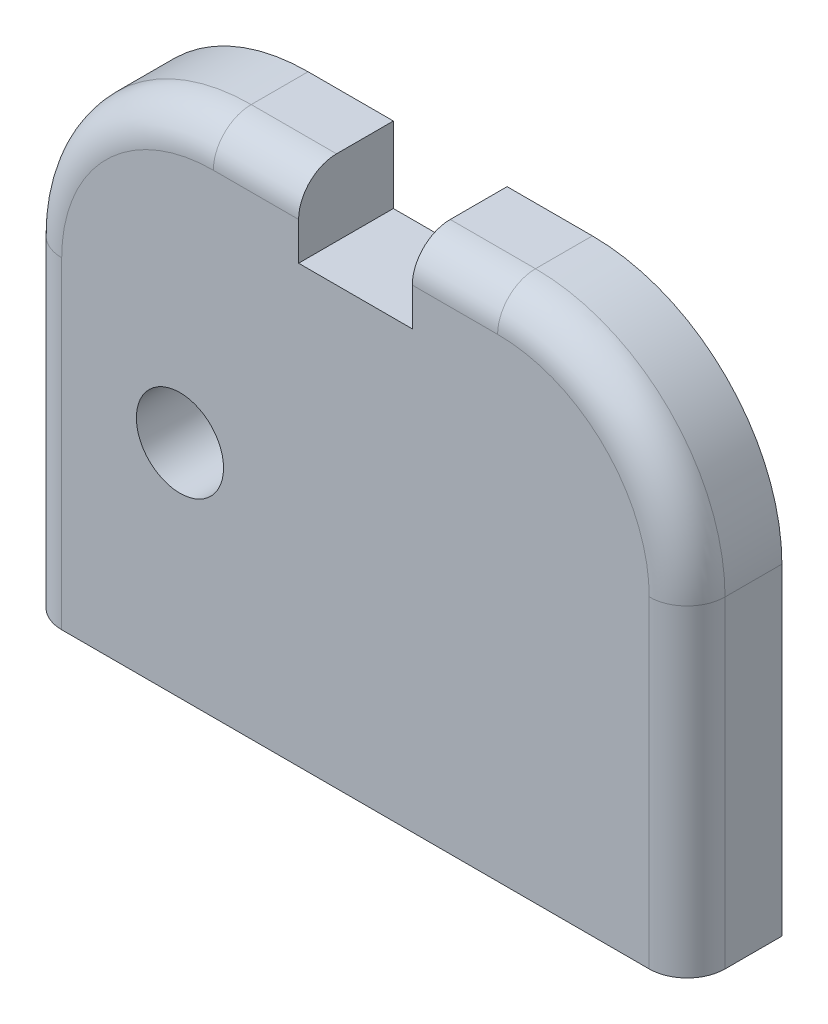
SolidWorks part; units mm, degrees
ref_plane "Piano frontale" through (0, 0, 0) normal (0, 0, 1) x (1, 0, 0)
ref_plane "Piano superiore" through (0, 0, 0) normal (0, 1, 0) x (1, 0, 0)
ref_plane "Piano destro" through (0, 0, 0) normal (1, 0, 0) x (0, 0, -1)
sketch "Sketch1" plane through (0, 0, 0) normal (0, 0, 1) x (1, 0, 0)
  line L0 (3, 13.5) -> (3, 9.5)
  line L1 (-17.5, -13.5) -> (17.5, -13.5)
  line L2 (-17.5, -13.5) -> (-17.5, 13.5)
  line L3 (-17.5, 13.5) -> (-3, 13.5)
  line L4 (17.5, -13.5) -> (17.5, 13.5)
  line L5 (-17.5, -13.5) -> (17.5, 13.5) construction
  line L6 (-17.5, 13.5) -> (17.5, -13.5) construction
  line L7 (3, 9.5) -> (-3, 9.5)
  line L8 (-3, 9.5) -> (-3, 13.5)
  line L9 (3, 13.5) -> (17.5, 13.5)
  point P0 (0, 0)
  dimension "D1" = 35
  dimension "D2" = 27
extrude "Boss-Extrude1" add sketch "Sketch1" along normal blind 5
fillet "Fillet1" radius 10 2 edges at (-17.5, 13.5, 2.5) (17.5, 13.5, 2.5)
fillet "Fillet2" radius 2 6 edges at (5.25, 13.5, 5) (14.5711, 10.5711, 5) (-5.25, 13.5, 5) (-14.5711, 10.5711, 5) (17.5, -5, 5) (-17.5, -5, 5)
sketch "Sketch2" plane through (0, 0, 0) normal (0, 0, -1) x (-1, 0, 0)
  circle A0 centre (9.2614, -1.8404) radius 6.5
  circle A1 centre (-9.15, -2) radius 6.2
  circle A2 centre (9.2614, -1.8404) radius 2.3
extrude "Boss-Extrude2" add sketch "Sketch2" along normal blind 1
sketch "Sketch3" plane through (0, 0, -1) normal (0, 0, -1) x (-1, 0, 0)
  circle A0 centre (-9.15, -2) radius 2.3
  dimension "D1" = 4.6
fillet "Fillet3" radius 1.5 2 edges at (-2.7614, -1.8404, 0) (15.35, -2, 0)
hole_wizard "Tap Drill Slot for M2 Tap1" positions "Sketch6" profile "Sketch7" size "M2" standard "ISO" slot yes
sketch "Sketch6" plane through (0, -13.5, 0) normal (0, -1, 0) x (-1, 0, 0)
  point P0 (-10.0075, -2.5052)
  point P2 (0, -2.5052)
  point P4 (10, -2.5)
sketch "Sketch7" plane through (10.0075, -13.5, 2.5052) normal (1, 0, 0) x (0, 0, -1)
  line L0 (0, 0) -> (0, 4.4807)
  line L1 (0, 4.4807) -> (0.8, 4)
  line L2 (0.8, 4) -> (0.8, 0)
  line L5 (0.8, 0) -> (0, 0)
  line L10 (0, 4.4807) -> (-0.8, 4) construction
  line L11 (0, -6.35) -> (0, 107.95) construction
  dimension "Hole Dia." = 1.6
  dimension "Hole Depth" = 4
  dimension "Drill Angle" = 118
extrude "Boss-Extrude3" add sketch "Sketch3" along normal blind 2
sketch "Sketch8" plane through (0, 0, 5) normal (0, 0, 1) x (1, 0, 0)
  circle A0 centre (-9.2614, -1.8404) radius 2.3 construction
  circle A1 centre (-9.2614, -1.8404) radius 2.3
extrude "Cut-Extrude1" cut sketch "Sketch8" against normal blind 10
